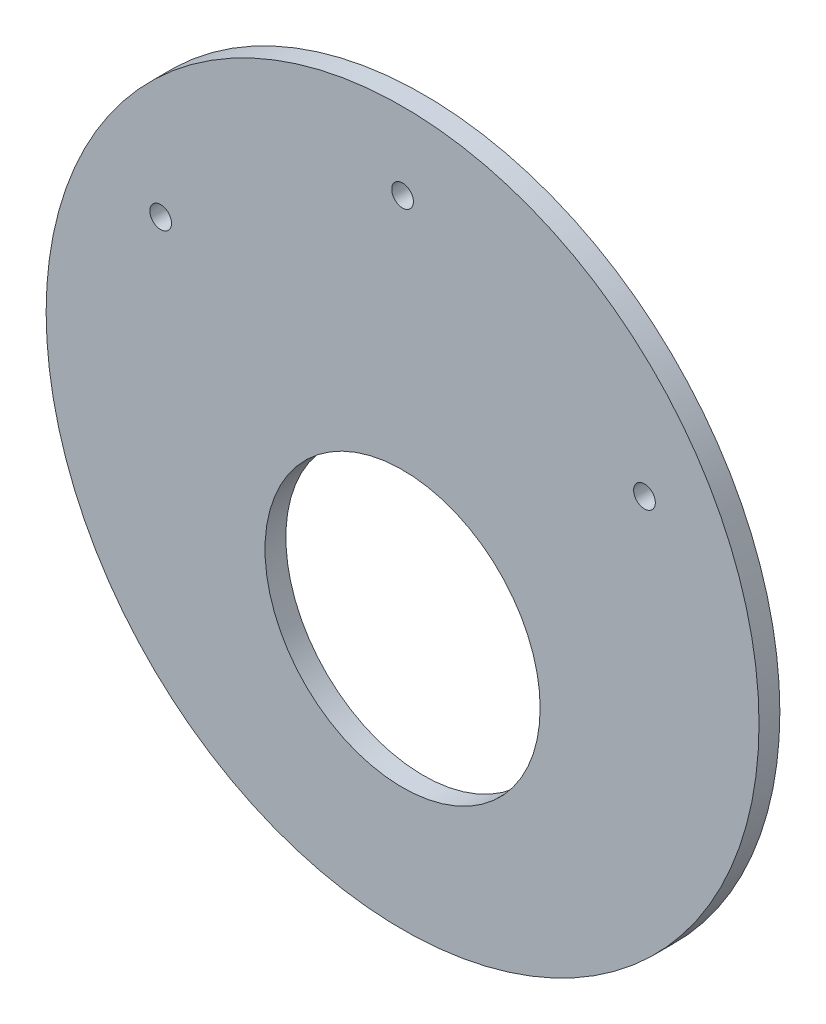
SolidWorks part; units mm, degrees
ref_plane "Front Plane" through (0, 0, 0) normal (0, 0, 1) x (1, 0, 0)
ref_plane "Top Plane" through (0, 0, 0) normal (0, 1, 0) x (1, 0, 0)
ref_plane "Right Plane" through (0, 0, 0) normal (1, 0, 0) x (0, 0, -1)
sketch "Sketch2" plane through (0, 0, 0) normal (0, 0, 1) x (1, 0, 0)
  circle A0 centre (0, 0) radius 85.5
  dimension "D1" = 171
extrude "Boss-Extrude1" add sketch "Sketch2" along normal blind 5
sketch "Sketch3" plane through (0, 0, 5) normal (0, 0, 1) x (1, 0, 0)
  circle A0 centre (0, 0) radius 67 construction
  circle A1 centre (0, -23) radius 33
  point P5 (0, 0)
  dimension "D1" = 134
  dimension "D2" = 66
  dimension "D3" = 23
extrude "Cut-Extrude1" cut sketch "Sketch3" against normal through all
sketch "Sketch4" plane through (0, 0, 5) normal (0, 0, 1) x (1, 0, 0)
  circle A0 centre (0, 0) radius 67 construction
  circle A1 centre (0, 67) radius 2.6
  point P5 (0, 0)
  dimension "D1" = 134
  dimension "D2" = 5.2
extrude "Cut-Extrude2" cut sketch "Sketch4" against normal through all
pattern_circular "CirPattern3" count 2 over 60 about axis through (0, 0, 5) along (0, 0, 1) of "Cut-Extrude2"
pattern_circular "CirPattern4" count 2 over 60 about axis through (0, 0, 5) along (0, 0, 1) of "CirPattern3" reverse direction yes
